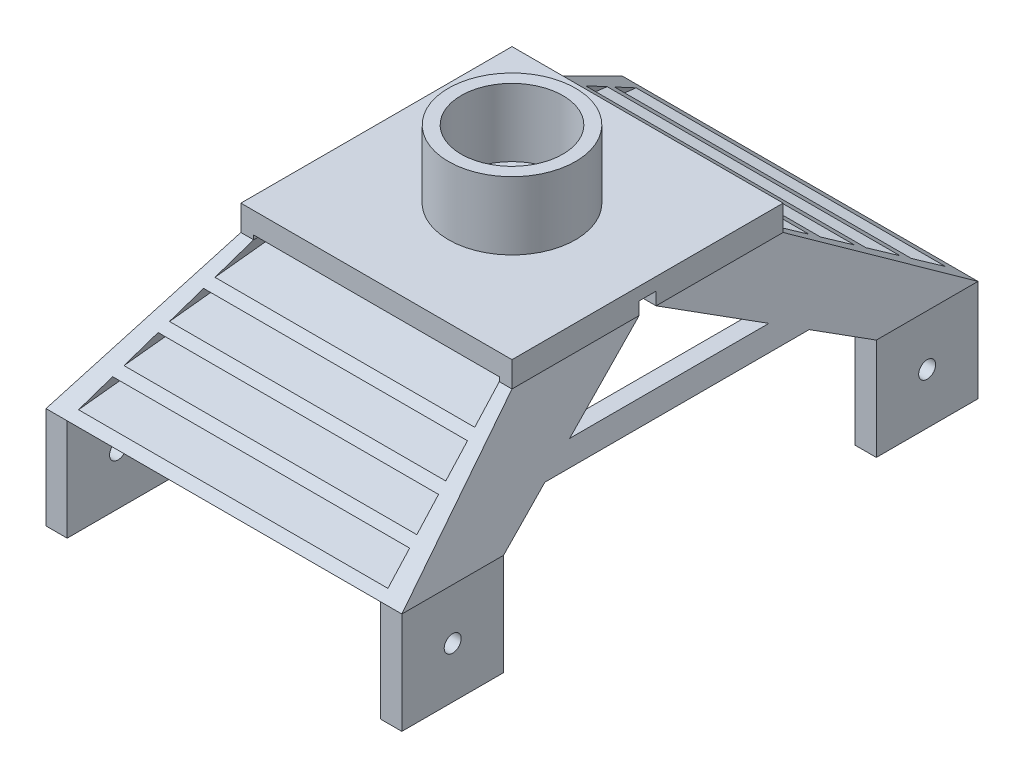
SolidWorks part; units mm, degrees
other "Markup1"
sketch "Sketch35" plane through (-42, -51, 68) normal (-0.7034, -0.6787, 0.2114) x (0.243, 0.0499, 0.9687)
material "ABS"
ref_plane "前视基准面" through (0, 0, 0) normal (0, 0, 1) x (1, 0, 0)
ref_plane "上视基准面" through (0, 0, 0) normal (0, 1, 0) x (1, 0, 0)
ref_plane "右视基准面" through (0, 0, 0) normal (1, 0, 0) x (0, 0, -1)
other "Configuration Table"
sketch "Sketch4" plane through (0, 0, 0) normal (0, 1, 0) x (1, 0, 0)
  line L0 (0, 0) -> (2.5882, 9.6593) construction
  line L1 (32, -32) -> (-32, -32)
  line L2 (32, -32) -> (32, 32)
  line L3 (32, 32) -> (-32, 32)
  line L4 (-32, -32) -> (-32, 32)
  line L5 (32, -32) -> (-32, 32) construction
  line L6 (32, 32) -> (-32, -32) construction
  line L7 (-2.5882, 9.6593) -> (-2.2, 8.2104)
  line L8 (2.5882, 9.6593) -> (2.2, 8.2104)
  line L9 (-32, 0) -> (32, 0) construction
  line L10 (-2.5882, -9.6593) -> (-2.2, -8.2104)
  line L11 (2.5882, -9.6593) -> (2.2, -8.2104)
  circle A0 centre (0, 0) radius 2.5
  arc A1 (2.5882, 9.6593) -> (-2.5882, 9.6593) centre (0, 0) ccw
  arc A2 (2.2, 8.2104) -> (-2.2, 8.2104) centre (0, 0) ccw
  arc A3 (2.5882, -9.6593) -> (-2.5882, -9.6593) centre (0, 0) cw
  arc A4 (2.2, -8.2104) -> (-2.2, -8.2104) centre (0, 0) cw
  point P0 (0, 0)
  dimension "D3" = 30
  dimension "D1" = 64
  dimension "D2" = 64
extrude "Boss-Extrude3" add sketch "Sketch4" along normal blind 3
sketch "Sketch6" plane through (0, 3, 0) normal (0, 1, 0) x (1, 0, 0)
  circle A0 centre (0, 0) radius 15
  circle A1 centre (0, 0) radius 12
extrude "Boss-Extrude4" add sketch "Sketch6" along normal blind 16
ref_plane "Plane1" through (0, -50, 0) normal (0, 1, 0) x (1, 0, 0)
sketch "Sketch8" plane through (0, -50, 0) normal (0, 1, 0) x (1, 0, 0)
  line L0 (0, -32) -> (0, 32) construction
  line L3 (-32, 0) -> (32, 0) construction
  line L7 (37, -68) -> (42, -68)
  line L8 (37, -68) -> (37, -44)
  line L9 (37, -44) -> (42, -44)
  line L10 (42, -68) -> (42, -44)
  line L18 (-37, -44) -> (-42, -44)
  line L19 (-42, -68) -> (-42, -44)
  line L20 (-37, -68) -> (-42, -68)
  line L21 (-37, -68) -> (-37, -44)
  line L22 (37, 44) -> (42, 44)
  line L23 (42, 68) -> (42, 44)
  line L24 (37, 68) -> (42, 68)
  line L25 (37, 68) -> (37, 44)
  line L26 (-37, 68) -> (-37, 44)
  line L27 (-37, 68) -> (-42, 68)
  line L28 (-42, 68) -> (-42, 44)
  line L29 (-37, 44) -> (-42, 44)
  dimension "D1" = 5
  dimension "D2" = 37
  dimension "D3" = 24
  dimension "D4" = 44
sketch "Sketch12" plane through (0, 0, 0) normal (0, -1, 0) x (1, 0, 0)
  line L0 (-32, 0) -> (32, 0) construction
  line L1 (32, 32) -> (29, 32)
  line L2 (32, 32) -> (32, 2)
  line L3 (32, 2) -> (29, 2)
  line L4 (29, 32) -> (29, 2)
  line L5 (-32, -32) -> (-32, 32) construction
  line L6 (32, 32) -> (32, -32) construction
  line L7 (0, 32) -> (0, -32) construction
  line L8 (-32, 32) -> (32, 32) construction
  line L9 (32, -32) -> (-32, -32) construction
  line L10 (32, -2) -> (29, -2)
  line L11 (29, -32) -> (29, -2)
  line L12 (32, -32) -> (29, -32)
  line L13 (32, -32) -> (32, -2)
  line L14 (-32, 2) -> (-29, 2)
  line L15 (-29, 32) -> (-29, 2)
  line L16 (-32, 32) -> (-29, 32)
  line L17 (-32, 32) -> (-32, 2)
  line L18 (-32, -32) -> (-32, -2)
  line L19 (-32, -32) -> (-29, -32)
  line L20 (-29, -32) -> (-29, -2)
  line L21 (-32, -2) -> (-29, -2)
  dimension "D1" = 3
  dimension "D2" = 30
extrude "Boss-Extrude7" add sketch "Sketch8" along normal blind 24 separate body
sketch "Sketch16" plane through (0, 0, 0) normal (1, 0, 0) x (0, 0, -1)
  line L0 (-68, -26) -> (-68, -50) construction
  line L1 (68, -26) -> (68, -50) construction
  circle A0 centre (-56, -38) radius 2
  circle A1 centre (56, -38) radius 2
  dimension "D1" = 12
  dimension "D2" = 12
extrude "Cut-Extrude3" cut sketch "Sketch16" against normal blind 85
extrude "Cut-Extrude4" cut sketch "Sketch16<2>" along normal blind 114
sketch "Sketch16<2>" plane through (0, 0, 0) normal (1, 0, 0) x (0, 0, -1) same geometry as "Sketch16"
extrude "Boss-Extrude8" add sketch "Sketch12" along normal blind 3
loft "Loft4" add section face at (-30.5, -3, -17) section face at (-39.5, -26, -56) connector at (-29, -3, -32) connector at (-37, -26, -68)
loft "Loft5" add section face at (-30.5, -3, 17) section face at (-39.5, -26, 56) connector at (-32, -3, 32) connector at (-42, -26, 68)
loft "Loft6" add section face at (30.5, -3, -17) section face at (39.5, -26, -56) connector at (32, -3, -32) connector at (42, -26, -68)
loft "Loft7" add section face at (30.5, -3, 17) section face at (39.5, -26, 56) connector at (29, -3, 32) connector at (37, -26, 68)
sketch "Sketch23" plane through (0, 0, 0) normal (0, -1, 0) x (1, 0, 0)
  line L0 (29, 32) -> (29, 2) construction
  line L1 (-29, 32) -> (29, 32)
  line L2 (-29, 32) -> (-29, 30)
  line L3 (-29, 30) -> (29, 30)
  line L4 (29, 32) -> (29, 30)
  line L5 (-32, 0) -> (32, 0) construction
  line L6 (-32, -2) -> (-32, 2) construction
  line L7 (32, 2) -> (32, -2) construction
  line L8 (-29, 2) -> (-29, 32) construction
  line L9 (-29, 22) -> (29, 22)
  line L10 (-29, 22) -> (-29, 20)
  line L11 (-29, 20) -> (29, 20)
  line L12 (29, 22) -> (29, 20)
  line L13 (-29, -10) -> (29, -10)
  line L14 (-29, 12) -> (29, 12)
  line L15 (-29, 12) -> (-29, 10)
  line L16 (-29, 10) -> (29, 10)
  line L17 (29, 12) -> (29, 10)
  line L18 (29, -12) -> (29, -10)
  line L19 (-29, -12) -> (29, -12)
  line L20 (-29, -12) -> (-29, -10)
  line L21 (-29, -20) -> (29, -20)
  line L22 (29, -22) -> (29, -20)
  line L23 (-29, -22) -> (29, -22)
  line L24 (-29, -22) -> (-29, -20)
  line L25 (-29, -30) -> (29, -30)
  line L26 (29, -32) -> (29, -30)
  line L27 (-29, -32) -> (29, -32)
  line L28 (-29, -32) -> (-29, -30)
  dimension "D1" = 2
  dimension "D2" = 2
  dimension "D3" = 8
  dimension "D4" = 2
  dimension "D5" = 8
extrude "Boss-Extrude14" add sketch "Sketch23" along normal blind 2
sketch "Sketch30" plane through (0, 0, 0) normal (1, 0, 0) x (0, 0, -1)
  line L0 (-17, -3) -> (-56, -26) construction
  line L1 (-2, -3) -> (-32, -3) construction
  line L2 (-68, -26) -> (-44, -26) construction
  line L3 (-68, -26) -> (-50.8819, -22.9816)
  line L4 (-65.8048, -24.5975) -> (-48.4257, -21.5331)
  line L5 (-32, -3) -> (-68, -26) construction
  line L6 (-41.0571, -17.1875) -> (-59.2191, -20.39)
  line L7 (-38.6009, -15.739) -> (-57.0239, -18.9875)
  line L8 (-31.2324, -11.3935) -> (-50.4382, -14.78)
  line L9 (-28.7762, -9.9449) -> (-48.243, -13.3775)
  line L10 (-21.4077, -5.5994) -> (-41.6573, -9.17)
  line L11 (-18.9515, -4.1509) -> (-39.4621, -7.7675)
  line L12 (-65.8048, -24.5975) -> (-68, -26)
  line L13 (-48.4257, -21.5331) -> (-50.8819, -22.9816)
  line L14 (-18.9515, -4.1509) -> (-21.4077, -5.5994)
  line L15 (-39.4621, -7.7675) -> (-41.6573, -9.17)
  line L16 (-48.243, -13.3775) -> (-50.4382, -14.78)
  line L17 (-57.0239, -18.9875) -> (-59.2191, -20.39)
  line L18 (-38.6009, -15.739) -> (-41.0571, -17.1875)
  line L19 (-28.7762, -9.9449) -> (-31.2324, -11.3935)
  dimension "D1" = 10
  dimension "D2" = 1
  dimension "D3" = 3
  dimension "D4" = 1
  dimension "D5" = 3
  dimension "D6" = 1
  dimension "D7" = 3
  dimension "D8" = 1
extrude "Boss-Extrude19" add sketch "Sketch30" along normal blind 45 and the other way blind 47
sketch "Sketch31" plane through (0, 0, 0) normal (0, 0, 1) x (1, 0, 0)
  line L0 (-32, -3) -> (-42, -26)
  line L1 (-42, -26) -> (-54.1068, -26)
  line L2 (-54.1068, -26) -> (-54.1068, -3)
  line L3 (-54.1068, -3) -> (-32, -3)
  line L4 (32, -3) -> (50.2676, -3)
  line L5 (50.2676, -3) -> (50.2676, -26)
  line L6 (50.2676, -26) -> (42, -26)
  line L7 (42, -26) -> (32, -3)
extrude "Cut-Extrude9" cut sketch "Sketch31" along normal blind 95
mirror "Mirror7" about plane through (0, 0, 0) normal (0, 0, 1) of "Cut-Extrude9", "Boss-Extrude19"
sketch "Sketch32" plane through (0, 0, 0) normal (0, 0, 1) x (1, 0, 0)
  line L22 (34.5609, -18.9875) -> (38.9511, -18.9875)
  line L23 (-34.5609, -18.9875) -> (34.5609, -18.9875) construction
  line L24 (33.0974, -14.78) -> (34.5609, -18.9875) construction
  line L25 (32, -3) -> (42, -26) construction
  line L26 (34.5609, -18.9875) -> (33.0974, -14.78)
  line L27 (33.0974, -14.78) -> (37.1217, -14.78)
  line L28 (37.1217, -14.78) -> (38.9511, -18.9875)
extrude "Boss-Extrude21" add sketch "Sketch32" along normal blind 44 and the other way blind 37
mirror "Mirror8" about plane through (0, 0, 0) normal (1, 0, 0) of "Boss-Extrude21"
ref_plane "Plane2" through (0, -15, 0) normal (0, 1, 0) x (1, 0, 0)
sketch "Sketch34" plane through (0, -15, 0) normal (0, 1, 0) x (1, 0, 0)
  line L0 (-32, 0) -> (49968, 0) construction
  line L3 (-32, 2) -> (-32, -2) construction
  line L8 (32, -2) -> (32, 2) construction
  line L10 (-9, -10) -> (-5, -10)
  line L11 (-9, -10) -> (-9, 10)
  line L12 (-9, 10) -> (-5, 10)
  line L13 (-5, -10) -> (-5, 10)
  line L14 (-9, -10) -> (-5, 10) construction
  line L15 (-9, 10) -> (-5, -10) construction
  point P4 (-32, 0)
  point P7 (32, 0)
  point P8 (-7, 0)
  point P14 (-5, 0)
  dimension "D1" = 5
  dimension "D2" = 4
  dimension "D3" = 20
extrude "Boss-Extrude23" add sketch "Sketch34" against normal blind 25
extrude "Boss-Extrude24" add sketch "Sketch34<2>" along normal blind 17 and the other way blind 35
sketch "Sketch34<2>" plane through (0, -15, 0) normal (0, 1, 0) x (1, 0, 0) same geometry as "Sketch34"
